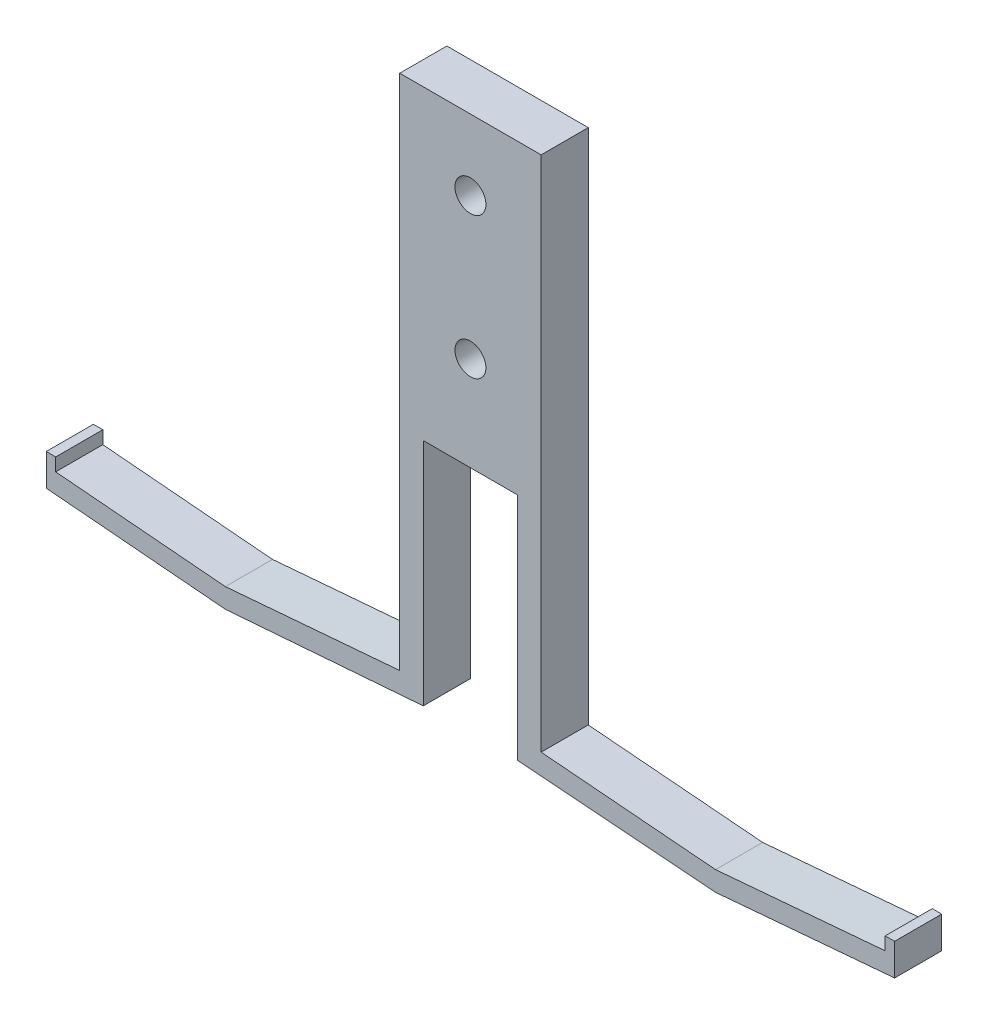
SolidWorks part; units mm, degrees
material "Nylon 6/10"
ref_plane "Front Plane" through (0, 0, 0) normal (0, 0, 1) x (1, 0, 0)
ref_plane "Top Plane" through (0, 0, 0) normal (0, 1, 0) x (1, 0, 0)
ref_plane "Right Plane" through (0, 0, 0) normal (1, 0, 0) x (0, 0, -1)
sketch "Sketch2" plane through (0, 0, 0) normal (0, 0, 1) x (1, 0, 0)
  line L1 (12.7, 0) -> (12.7, -61.918)
  line L2 (12.7, -61.918) -> (66.04, -66.0514)
  line L3 (66.04, -66.0514) -> (114.3, -61.918)
  line L4 (114.3, -61.918) -> (114.3, -53.3514)
  line L5 (111.76, -53.3514) -> (111.76, -56.838)
  line L6 (111.76, -56.838) -> (66.04, -60.7538)
  line L19 (114.3, -53.3514) -> (111.76, -53.3514)
  line L20 (0, 125.2351) -> (0, -75.9356) construction
  line L21 (12.7, 0) -> (-12.7, 0)
  line L22 (0, 0) -> (0, 82.55)
  line L23 (19.05, 82.55) -> (-19.05, 82.55)
  line L24 (19.05, 82.55) -> (19.05, 0)
  line L25 (19.05, 0) -> (19.05, -56.838)
  line L26 (19.05, -56.838) -> (66.04, -60.7538)
  line L27 (-19.05, 0) -> (-19.05, -56.838)
  line L28 (-19.05, 82.55) -> (-19.05, 0)
  line L29 (-12.7, 0) -> (-12.7, -61.918)
  line L30 (-12.7, -61.918) -> (-66.04, -66.0514)
  line L31 (-66.04, -66.0514) -> (-114.3, -61.918)
  line L32 (-114.3, -61.918) -> (-114.3, -53.3514)
  line L33 (-114.3, -53.3514) -> (-111.76, -53.3514)
  line L34 (-111.76, -53.3514) -> (-111.76, -56.838)
  line L35 (-111.76, -56.838) -> (-66.04, -60.7538)
  line L36 (-19.05, -56.838) -> (-66.04, -60.7538)
  dimension "D1" = 19.05
  dimension "D2" = 12.7
  dimension "D3" = 56.838
  dimension "D4" = 3.9158
  dimension "D5" = 61.918
  dimension "D6" = 2.54
  dimension "D7" = 45.72
  dimension "D8" = 46.99
  dimension "D9" = 12.7
  dimension "D10" = 82.55
extrude "Boss-Extrude1" add sketch "Sketch2" along normal blind 12.7 contours L26 L25 L24 L23 L22 L21 L1 L2 L3 L4 L19 L5 L6 | L27 L36 L35 L34 L33 L32 L31 L30 L29 L21 L22 L23 L28 region at (6.35, 1.8747, 0) region at (-6.35, 1.8747, 0)
hole_wizard "21/64 (0.32813) Diameter Hole1" positions "Sketch3" profile "Sketch4" hole size "21/64" standard "ANSI Inch" end condition through all
sketch "Sketch3" plane through (0, 0, 12.7) normal (0, 0, 1) x (1, 0, 0)
  point P0 (0, 25.4)
  point P2 (0, 63.5)
  dimension "D1" = 25.4
  dimension "D2" = 38.1
sketch "Sketch4" plane through (0, 25.4, 12.7) normal (1, 0, 0) x (0, -1, 0)
  line L0 (0, 0) -> (0, 12.7)
  line L1 (0, 12.7) -> (4.1673, 12.7)
  line L2 (4.1673, 12.7) -> (4.1673, 0)
  line L5 (4.1673, 0) -> (0, 0)
  line L11 (0, -6.35) -> (0, 107.95) construction
  dimension "Thru Hole Dia." = 8.3345
  dimension "Thru Hole Depth" = 12.7
